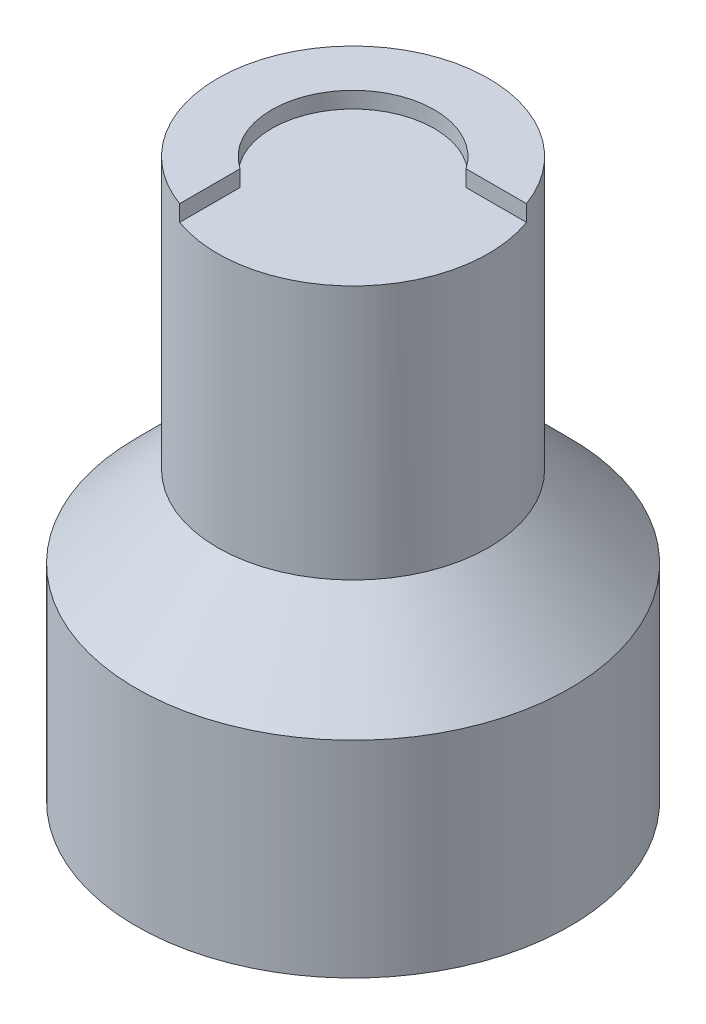
SolidWorks part; units mm, degrees
material "Простая углеродистая сталь"
ref_plane "Front" through (0, 0, 0) normal (0, 0, 1) x (1, 0, 0)
ref_plane "Top" through (0, 0, 0) normal (0, 1, 0) x (1, 0, 0)
ref_plane "Right" through (0, 0, 0) normal (1, 0, 0) x (0, 0, -1)
sketch "Эскиз1" plane through (0, 0, 0) normal (0, 0, 1) x (1, 0, 0)
  line L1 (0, 10.3) -> (-5, 10.3)
  line L9 (0, -10.3) -> (-8, -10.3)
  line L10 (0, 10.3) -> (0, -10.3)
  line L11 (-8, -10.3) -> (-8, 0.3)
  line L12 (-8, 0.3) -> (-5, 0.3)
  line L13 (-5, 0.3) -> (-5, 10.3)
  point P0 (0, 0)
  dimension "D1" = 10
  dimension "D2" = 8
  dimension "D5" = 5
  dimension "D6" = 20.6
revolve "База" add sketch "Эскиз1" angle 360 about L10
sketch "Эскиз4" plane through (0, 10.3, 0) normal (0, 1, 0) x (1, 0, 0)
  line L0 (0, 0) -> (5.3033, -5.3033) construction
  line L1 (2.4741, 1.6967) -> (5.3033, 1.6967)
  line L2 (-1.6967, -2.4741) -> (-1.6967, -5.3033)
  line L8 (-1.6967, -5.3033) -> (5.3033, -5.3033)
  line L9 (5.3033, 1.6967) -> (5.3033, -5.3033)
  arc A7 (2.4741, 1.6967) -> (-1.6967, -2.4741) centre (0, 0) ccw
  dimension "D3" = 6
  dimension "D1" = 45
  dimension "D2" = 7
  dimension "D4" = 7.5
extrude "Основание платы" cut sketch "Эскиз4" against normal blind 0.6
chamfer "Фаска1" distance 3 angle 45 1 edges at (-8, 0.3, 0)
sketch "Эскиз5" plane through (0, -10.3, 0) normal (0, -1, 0) x (1, 0, 0)
  circle A0 centre (0, 0) radius 5.1
  dimension "D1" = 10.2
extrude "Магнит" cut sketch "Эскиз5" against normal blind 5.1
hole_wizard "Крепление магнита M3" positions "Эскиз2" profile "Эскиз3" tap size "M3" standard "ISO"
sketch "Эскиз2" plane through (0, -5.2, 0) normal (0, -1, 0) x (-1, 0, 0)
  point P0 (0, 0)
cosmetic thread "Отверстие резьбы1" parameters "D1"=8, "D2"=3
sketch "Эскиз3" plane through (0, -5.2, 0) normal (1, 0, 0) x (0, 0, -1)
  line L0 (0, 0) -> (0, 10.7511)
  line L1 (0, 10.7511) -> (1.25, 10)
  line L2 (1.25, 10) -> (1.25, 0)
  line L5 (1.25, 0) -> (0, 0)
  line L10 (0, 10.7511) -> (-1.25, 10) construction
  line L11 (0, -6.35) -> (0, 107.95) construction
  dimension "Диаметр сверла" = 2.5
  dimension "Глубина сверла" = 10
  dimension "Угол заточки сверла" = 118
